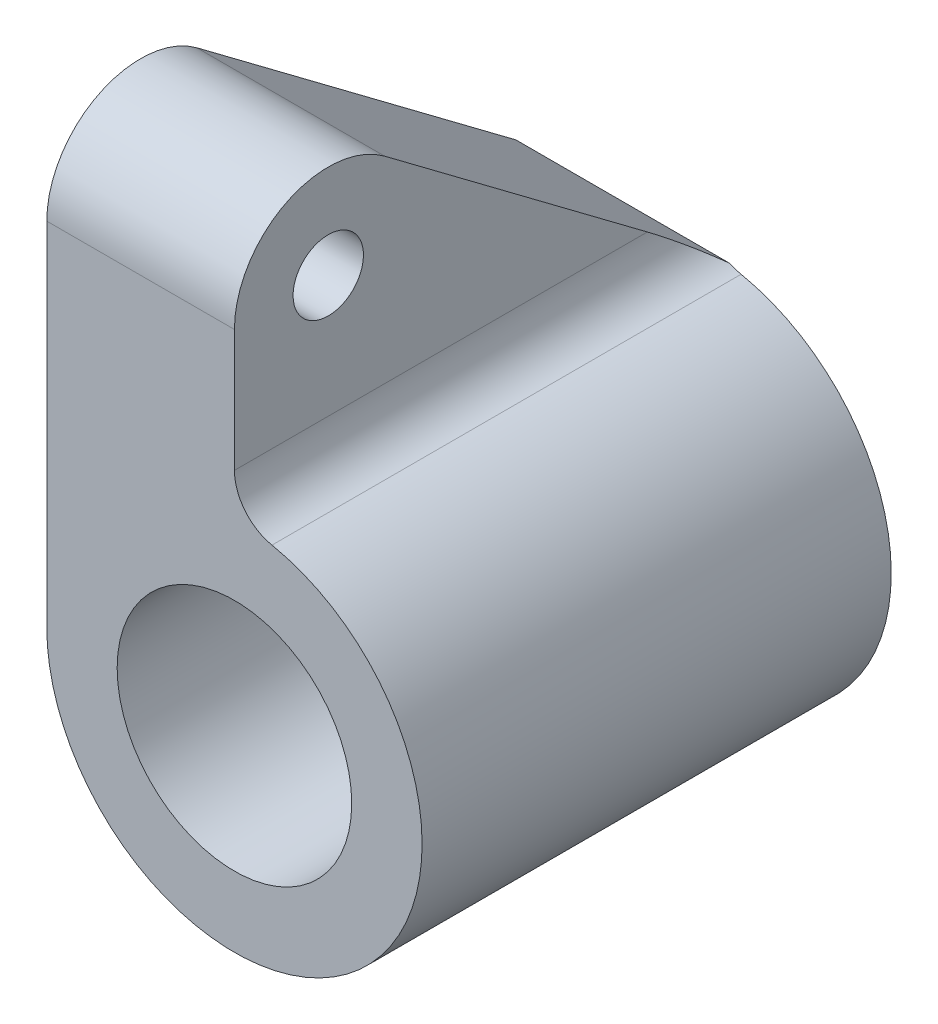
SolidWorks part; units mm, degrees
ref_plane "前视基准面" through (0, 0, 0) normal (0, 0, 1) x (1, 0, 0)
ref_plane "上视基准面" through (0, 0, 0) normal (0, 1, 0) x (1, 0, 0)
ref_plane "右视基准面" through (0, 0, 0) normal (1, 0, 0) x (0, 0, -1)
sketch "草图1" plane through (0, 0, 0) normal (0, 0, 1) x (1, 0, 0)
  circle A0 centre (0, 0) radius 5
  circle A1 centre (0, 0) radius 8
  dimension "D1" = 10
  dimension "D2" = 16
extrude "凸台-拉伸1" add sketch "草图1" along normal blind 20
sketch "草图2" plane through (0, 0, 20) normal (0, 0, 1) x (1, 0, 0)
  line L0 (-8, 0) -> (-8, 20)
  line L1 (-8, 20) -> (0, 20)
  line L2 (0, 20) -> (0, 8)
  circle A0 centre (0, 0) radius 8 construction
  arc A1 (0, 8) -> (-8, 0) centre (0, 0) ccw
  dimension "D1" = 20
  dimension "D2" = 8
extrude "凸台-拉伸2" add sketch "草图2" against normal through all
sketch "草图3" plane through (-8, 0, 0) normal (-1, 0, 0) x (0, 0, 1)
  line L0 (20, 20) -> (20, 0) construction
  line L1 (13.6, 18.2) -> (0, 8)
  line L3 (0, 8) -> (0, 20)
  line L4 (0, 20) -> (20, 20)
  line L5 (20, 20) -> (20, 15)
  line L6 (0, 8) -> (20, 8) construction
  line L7 (0, 8) -> (20, 8) construction
  line L8 (0, 0) -> (20, 0) construction
  circle A0 centre (16, 15) radius 1.5
  arc A1 (20, 15) -> (13.6, 18.2) centre (16, 15) ccw
  dimension "D1" = 3
  dimension "D2" = 8
  dimension "D3" = 15
extrude "切除-拉伸1" cut sketch "草图3" against normal through all
fillet "圆角1" radius 2 1 edges at (0, 8, 10)
